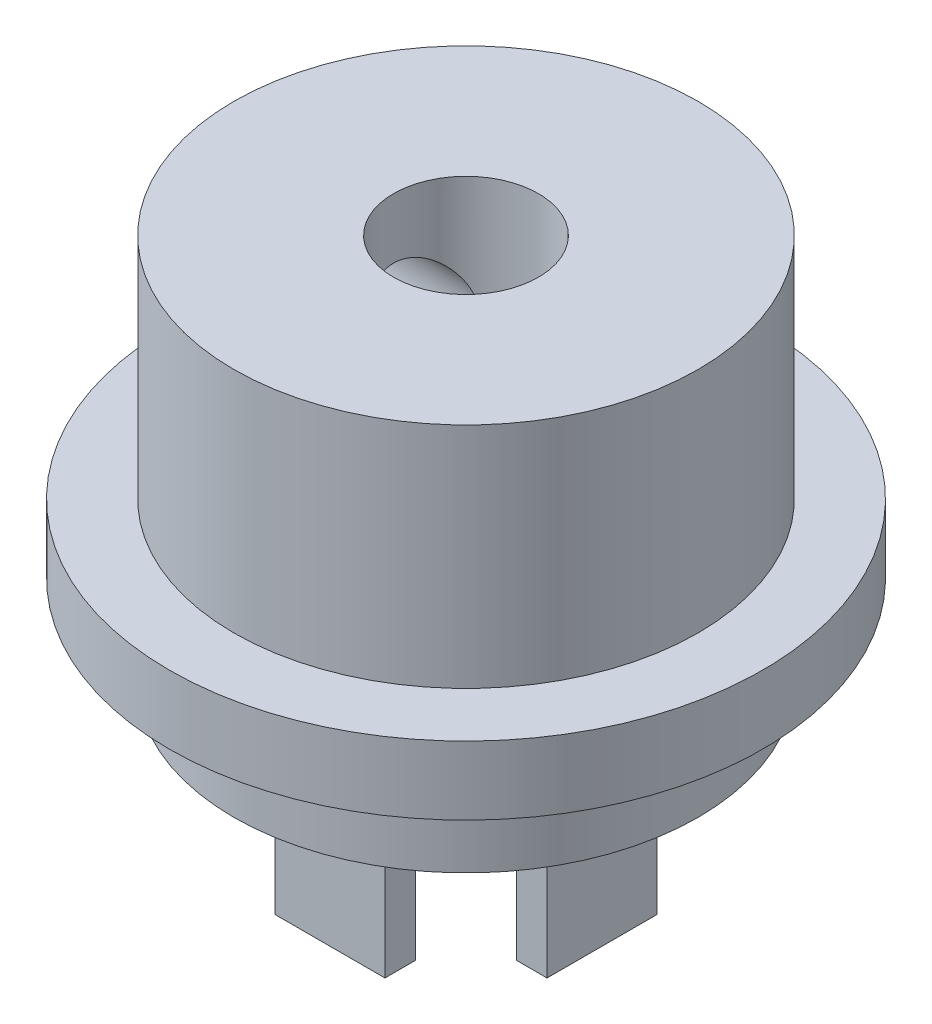
SolidWorks part; units mm, degrees
ref_plane "Front Plane" through (0, 0, 0) normal (0, 0, 1) x (1, 0, 0)
ref_plane "Top Plane" through (0, 0, 0) normal (0, 1, 0) x (1, 0, 0)
ref_plane "Right Plane" through (0, 0, 0) normal (1, 0, 0) x (0, 0, -1)
sketch "Sketch1" plane through (0, 0, 0) normal (0, 1, 0) x (1, 0, 0)
  circle A0 centre (0, 0) radius 3.175
  circle A1 centre (0, 0) radius 10.175
  circle A2 centre (0, 0) radius 13
  point P25 (0, 0)
extrude "Boss-Extrude1" add sketch "Sketch1" along normal blind 10 and the other way blind 7 contours A1 A0 region at (-9.8872, 0, 0)
extrude "Boss-Extrude2" add sketch "Sketch1<3>" against normal blind 3 separate body contours A2 A1 region at (-12.6323, 0, 0)
sketch "Sketch1<3>" plane through (0, 0, 0) normal (0, 1, 0) x (1, 0, 0) same geometry as "Sketch1"
sketch "Sketch2" plane through (0, 0, 0) normal (1, 0, 0) x (0, 0, -1)
  circle A0 centre (0, 4.8641) radius 2.5
  point P2 (0.8561, 5.9382)
  point P3 (0, 0)
  point P5 (0, 4.8641)
  point P6 (0, 0)
  point P7 (0, 0)
extrude "Cut-Extrude1" cut sketch "Sketch2" against normal blind 11
sketch "Sketch3" plane through (0, -7, 0) normal (0, -1, 0) x (1, 0, 0)
  line L0 (5.9593, 2.4074) -> (5.9593, -2.4074)
  line L1 (-2.4074, 5.9593) -> (2.4074, 5.9593)
  line L2 (-2.4074, 5.9593) -> (-2.4074, 4.6112)
  line L3 (-2.4074, 4.6112) -> (2.4074, 4.6112)
  line L4 (2.4074, 5.9593) -> (2.4074, 4.6112)
  line L5 (-2.4074, 5.9593) -> (2.4074, 4.6112) construction
  line L6 (-2.4074, 4.6112) -> (2.4074, 5.9593) construction
  line L7 (5.9593, -2.4074) -> (4.6112, -2.4074)
  line L8 (4.6112, 2.4074) -> (4.6112, -2.4074)
  line L9 (5.9593, 2.4074) -> (4.6112, 2.4074)
  line L10 (2.4074, -5.9593) -> (-2.4074, -5.9593)
  line L11 (-2.4074, -5.9593) -> (-2.4074, -4.6112)
  line L12 (2.4074, -4.6112) -> (-2.4074, -4.6112)
  line L13 (2.4074, -5.9593) -> (2.4074, -4.6112)
  line L14 (-5.9593, -2.4074) -> (-5.9593, 2.4074)
  line L15 (-5.9593, 2.4074) -> (-4.6112, 2.4074)
  line L16 (-4.6112, -2.4074) -> (-4.6112, 2.4074)
  line L17 (-5.9593, -2.4074) -> (-4.6112, -2.4074)
  point P0 (0, 5.2852)
  point P21 (0, 0)
extrude "Boss-Extrude3" add sketch "Sketch3" along normal blind 7
